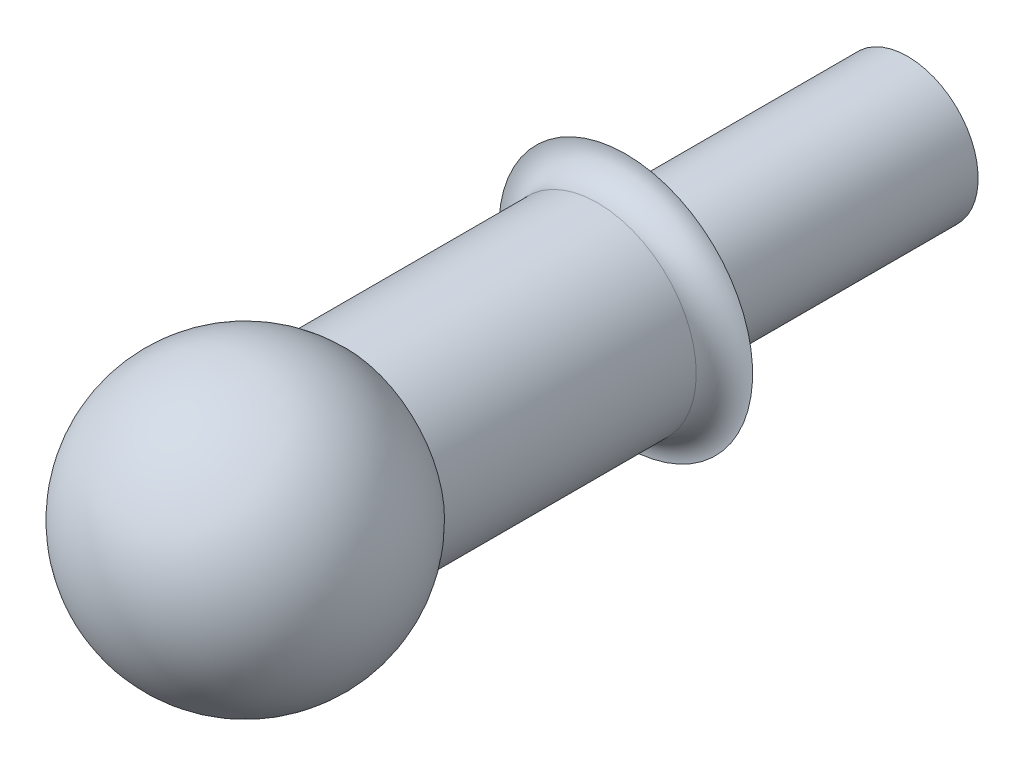
SolidWorks part; units mm, degrees
ref_plane "Front Plane" through (0, 0, 0) normal (0, 0, 1) x (1, 0, 0)
ref_plane "Top Plane" through (0, 0, 0) normal (0, 1, 0) x (1, 0, 0)
ref_plane "Right Plane" through (0, 0, 0) normal (1, 0, 0) x (0, 0, -1)
sketch "Sketch2" plane through (0, 0, 0) normal (0, 0, 1) x (1, 0, 0)
  line L0 (80, 0) -> (-42.1921, 0) construction
  line L2 (-22, -5.5) -> (80, -5.5)
  line L3 (80, -5.5) -> (80, 5.5)
  line L4 (0, 24.5757) -> (0, -40.5685) construction
  line L6 (-22, 5.5) -> (80, 5.5)
  line L7 (-1.5811, -2.25) -> (1.5811, -2.25)
  arc A0 (-22, 5.5) -> (-22, -5.5) centre (-22, 0) ccw
  arc A3 (1.5811, -2.25) -> (-1.5811, -2.25) centre (0, 0) ccw
  point P14 (0, 2.75)
  dimension "D1" = 5.5
  dimension "D5" = 2.75
  dimension "D2" = 80
  dimension "D3" = 22
  dimension "D4" = 5
extrude "Boss-Extrude2" add sketch "Sketch2" along normal mid plane 10
sketch "Sketch3" plane through (80, 0, 0) normal (1, 0, 0) x (0, 0, -1)
  line L0 (33.5, 0) -> (-33.5, 0) construction
  line L1 (-33.5, 0) -> (-33.5, 3.5)
  line L2 (-33.5, 3.5) -> (-21, 3.5)
  line L3 (-20, 4.5) -> (-20, 5)
  line L4 (-19.5, 5.5) -> (19.5, 5.5)
  line L5 (20, 5) -> (20, 4.5)
  line L6 (21, 3.5) -> (33.5, 3.5)
  line L7 (33.5, 3.5) -> (33.5, 0)
  line L8 (33.5, 0) -> (-33.5, 0)
  arc A0 (-21, 3.5) -> (-20, 4.5) centre (-21, 4.5) ccw
  arc A1 (20, 4.5) -> (21, 3.5) centre (21, 4.5) ccw
  arc A2 (-20, 5) -> (-19.5, 5.5) centre (-19.5, 5) cw
  arc A3 (19.5, 5.5) -> (20, 5) centre (19.5, 5) cw
  point P12 (20, 4.75)
  point P13 (0, 5.5)
  point P17 (-20, 5.5)
  point P20 (20, 5.5)
  dimension "D7" = 1
  dimension "D8" = 1
  dimension "D9" = 0.5
  dimension "D10" = 0.5
  dimension "D1" = 40
  dimension "D2" = 13.5
  dimension "D3" = 13.5
  dimension "D4" = 3.5
  dimension "D5" = 5.5
  dimension "D6" = 3.5
revolve "Revolve12" add sketch "Sketch3" angle 360 about L0
sketch "Sketch5" plane through (0, 0, -33.5) normal (0, 0, -1) x (-1, 0, 0)
  line L0 (-80, 5) -> (-80, -5) construction
  line L1 (-80, 5) -> (-80, -5)
  circle A0 centre (-80, 0) radius 5 construction
  arc A1 (-80, 5) -> (-80, -5) centre (-80, 0) ccw
revolve "Revolve16" add sketch "Sketch5" angle 360 about L0
sketch "Sketch6" plane through (0, 0, 33.5) normal (0, 0, 1) x (1, 0, 0)
  line L0 (80, 5) -> (80, -5) construction
  line L1 (80, 5) -> (80, -5)
  circle A0 centre (80, 0) radius 5 construction
  arc A1 (80, 5) -> (80, -5) centre (80, 0) ccw
revolve "Revolve17" add sketch "Sketch6" angle 360 about L0
sketch "Sketch8" plane through (0, 0, 5) normal (0, 0, 1) x (1, 0, 0)
  line L0 (-1.5811, -2.25) -> (1.5811, -2.25)
  circle A0 centre (0, 0) radius 5.5
  arc A1 (1.5811, -2.25) -> (-1.5811, -2.25) centre (0, 0) ccw
  point P6 (0, 2.75)
  dimension "D1" = 2.75
  dimension "D2" = 2.75
  dimension "D3" = 5
extrude "Boss-Extrude5" add sketch "Sketch8" along normal mid plane 20
fillet "Fillet1" radius 2 2 edges at (-5.5, 0, 5) (5.5, 0, 5)
sketch "Sketch9" plane through (0, -2.25, 0) normal (0, 1, 0) x (1, 0, 0)
  line L0 (0, -15) -> (0, -5) construction
  line L1 (-5.5, -15) -> (5.5, -15) construction
  circle A0 centre (0, -10) radius 1.5
  dimension "D1" = 3
extrude "Cut-Extrude1" cut sketch "Sketch9" against normal blind 10
sketch "Sketch10" plane through (0, 5.5, 0) normal (0, 1, 0) x (1, 0, 0)
  line L0 (75.5, -20) -> (84.5, -20) construction
  line L1 (91.6988, -20) -> (-40.0433, -20)
  line L2 (91.6988, -20) -> (91.6988, 40.8738)
  line L3 (91.6988, 40.8738) -> (-40.0433, 40.8738)
  line L4 (-40.0433, -20) -> (-40.0433, 40.8738)
extrude "Cut-Extrude2" cut sketch "Sketch10" against normal blind 30
sketch "Sketch11" plane through (0, 0, 20) normal (0, 0, -1) x (-1, 0, 0)
  line L0 (-78.1002, 1.625) -> (-78.1002, -1.625)
  arc A0 (-78.1002, 1.625) -> (-78.1002, -1.625) centre (-80, 0) ccw
  dimension "D1" = 5
  dimension "D2" = 3.25
extrude "Boss-Extrude6" add sketch "Sketch11" along normal blind 10
